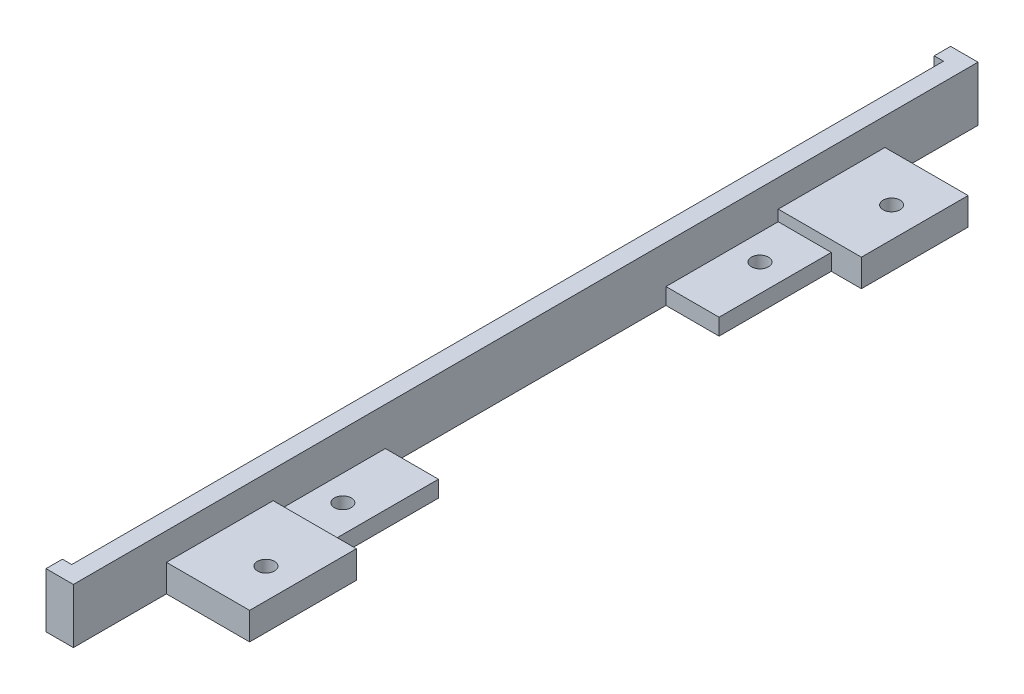
SolidWorks part; units mm, degrees
ref_plane "Front Plane" through (0, 0, 0) normal (0, 0, 1) x (1, 0, 0)
ref_plane "Top Plane" through (0, 0, 0) normal (0, 1, 0) x (1, 0, 0)
ref_plane "Right Plane" through (0, 0, 0) normal (1, 0, 0) x (0, 0, -1)
sketch "Sketch1" plane through (0, 0, 0) normal (0, 1, 0) x (1, 0, 0)
  line L0 (0, 0) -> (5, 0)
  line L1 (5, 0) -> (5, 17)
  line L2 (5, 17) -> (20.2, 17)
  line L3 (20.2, 17) -> (20.2, 36.5)
  line L4 (20.2, 36.5) -> (14.7, 36.5)
  line L5 (14.7, 36.5) -> (14.7, 57)
  line L6 (14.7, 57) -> (5, 57)
  line L7 (5, 57) -> (5, 108.26)
  line L8 (0, 0) -> (0, 3)
  line L9 (0, 3) -> (1.7, 3)
  line L10 (1.7, 3) -> (1.7, 162.26)
  line L11 (5, 82.63) -> (1.7, 82.63) construction
  line L12 (14.7, 108.26) -> (5, 108.26)
  line L13 (14.7, 128.76) -> (14.7, 108.26)
  line L14 (20.2, 128.76) -> (14.7, 128.76)
  line L15 (20.2, 148.26) -> (20.2, 128.76)
  line L16 (5, 148.26) -> (20.2, 148.26)
  line L17 (5, 165.26) -> (5, 148.26)
  line L18 (0, 162.26) -> (1.7, 162.26)
  line L19 (0, 165.26) -> (5, 165.26)
  line L20 (0, 165.26) -> (0, 162.26)
  circle A0 centre (14.7, 25.48) radius 1.55
  circle A1 centre (9.7, 44.53) radius 1.55
  circle A2 centre (9.7, 120.73) radius 1.55
  circle A3 centre (14.7, 139.78) radius 1.55
  point P31 (0, 0)
  point P33 (0, 0)
  point P35 (0, 0)
  dimension "D10" = 3.1
  dimension "D11" = 3.1
  dimension "D12" = 76.2
  dimension "D13" = 114.3
  dimension "D1" = 5
  dimension "D2" = 3
  dimension "D3" = 17
  dimension "D4" = 19.5
  dimension "D5" = 40
  dimension "D6" = 159.26
  dimension "D7" = 3.3
  dimension "D8" = 18.5
  dimension "D9" = 13
  dimension "D14" = 8
extrude "Boss-Extrude1" add sketch "Sketch1" along normal blind 10
sketch "Sketch3" plane through (0, 10, 0) normal (0, 1, 0) x (1, 0, 0)
  line L0 (5, 148.26) -> (20.2, 148.26)
  line L1 (20.2, 148.26) -> (20.2, 17)
  line L2 (20.2, 17) -> (5, 17)
  line L3 (5, 17) -> (5, 148.26)
extrude "Cut-Extrude1" cut sketch "Sketch3" against normal blind 5
sketch "Sketch4" plane through (0, 5, 0) normal (0, 1, 0) x (1, 0, 0)
  line L0 (14.7, 128.76) -> (14.7, 36.5)
  line L1 (14.7, 36.5) -> (5, 36.5)
  line L2 (5, 57) -> (5, 17) construction
  line L3 (5, 36.5) -> (5, 128.76)
  line L4 (5, 148.26) -> (5, 108.26) construction
  line L5 (5, 128.76) -> (14.7, 128.76)
extrude "Cut-Extrude2" cut sketch "Sketch4" against normal blind 2
sketch "Sketch5" plane through (0, 0, 0) normal (0, -1, 0) x (1, 0, 0)
  line L0 (14.7, -25.48) -> (17.45, -25.48) construction
  line L1 (17.45, -23.8923) -> (17.45, -27.0677)
  line L2 (14.7, -25.48) -> (16.075, -27.8616) construction
  line L3 (17.45, -27.0677) -> (14.7, -28.6554)
  line L4 (14.7, -25.48) -> (13.325, -27.8616) construction
  line L5 (14.7, -28.6554) -> (11.95, -27.0677)
  line L6 (14.7, -25.48) -> (11.95, -25.48) construction
  line L7 (11.95, -27.0677) -> (11.95, -23.8923)
  line L8 (14.7, -25.48) -> (13.325, -23.0984) construction
  line L9 (11.95, -23.8923) -> (14.7, -22.3046)
  line L10 (14.7, -25.48) -> (16.075, -23.0984) construction
  line L11 (14.7, -22.3046) -> (17.45, -23.8923)
  line L12 (1.7, -82.63) -> (14.7, -82.63) construction
  line L13 (1.7, -162.26) -> (1.7, -3) construction
  line L14 (11.95, -138.1923) -> (11.95, -141.3677)
  line L15 (14.7, -136.6046) -> (11.95, -138.1923)
  line L16 (17.45, -138.1923) -> (14.7, -136.6046)
  line L17 (17.45, -141.3677) -> (17.45, -138.1923)
  line L18 (14.7, -142.9554) -> (17.45, -141.3677)
  line L19 (11.95, -141.3677) -> (14.7, -142.9554)
  point P7 (17.45, -25.48)
  point P25 (14.7, -25.48)
  dimension "D1" = 6
  dimension "D2" = 5.5
extrude "Cut-Extrude4" cut sketch "Sketch5" against normal blind 2.3
